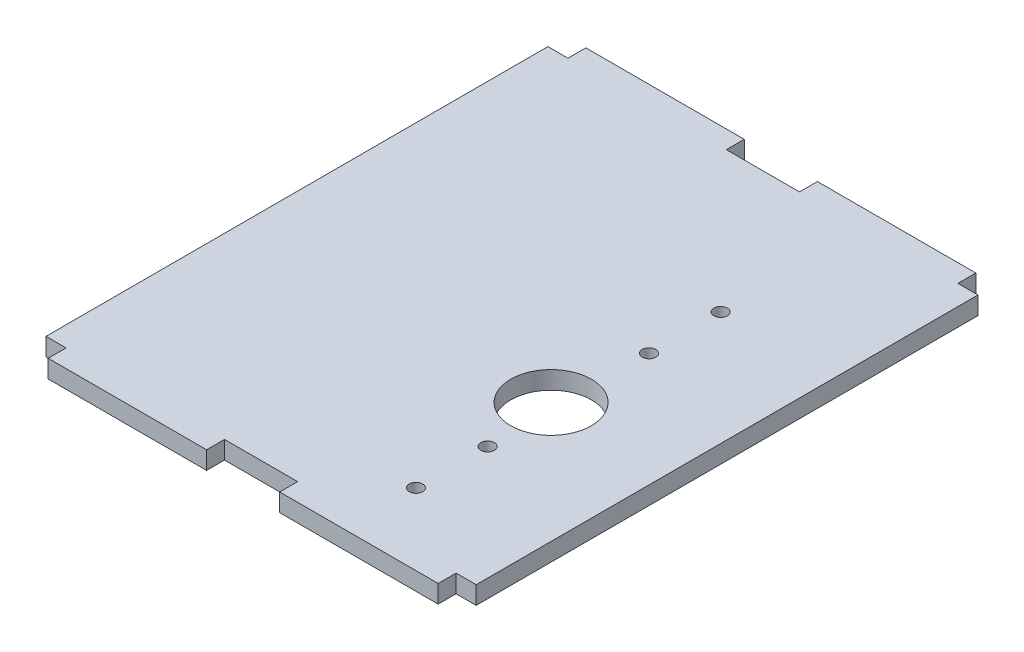
SolidWorks part; units mm, degrees
ref_plane "Front Plane" through (0, 0, 0) normal (0, 0, 1) x (1, 0, 0)
ref_plane "Top Plane" through (0, 0, 0) normal (0, 1, 0) x (1, 0, 0)
ref_plane "Right Plane" through (0, 0, 0) normal (1, 0, 0) x (0, 0, -1)
sketch "Sketch1" plane through (0, 0, 0) normal (0, 1, 0) x (1, 0, 0)
  line L1 (0, 0) -> (304.8, 0)
  line L2 (0, 0) -> (0, 355.6)
  line L3 (0, 355.6) -> (304.8, 355.6)
  line L4 (304.8, 0) -> (304.8, 355.6)
  ellipse E1 centre (219.5122, 138.3861) end of major axis (248.0872, 138.3861) minor radius 28.574
  dimension "D1" = 355.6
  dimension "D2" = 304.8
extrude "Boss-Extrude1" add sketch "Sketch1" along normal blind 12.7
sketch "Sketch2" plane through (0, 0, 0) normal (0, -1, 0) x (1, 0, 0)
  line L0 (0, 0) -> (304.8, 0) construction
  line L1 (0, -355.6) -> (0, 0) construction
  circle A0 centre (224.028, -38.1) radius 4.7625
  circle A1 centre (224.028, -88.9) radius 4.7625
  circle A2 centre (224.028, -203.2) radius 4.7625
  circle A3 centre (224.028, -254) radius 4.7625
  dimension "D3" = 88.9
  dimension "D6" = 9.525
  dimension "D1" = 38.1
  dimension "D2" = 224.028
  dimension "D4" = 203.2
  dimension "D5" = 254
  dimension "D7" = 224.028
  dimension "D8" = 224.028
  dimension "D9" = 224.028
extrude "Cut-Extrude1" cut sketch "Sketch2" against normal blind 12.7
sketch "Sketch3" plane through (0, 12.7, 0) normal (0, 1, 0) x (1, 0, 0)
  line L0 (152.4, 355.6) -> (152.4, 250.206) construction
  line L1 (0, 177.8) -> (22.2548, 177.8) construction
  line L2 (14.224, 355.6) -> (126.492, 355.6)
  line L3 (14.224, 355.6) -> (14.224, 368.3)
  line L4 (0, 355.6) -> (0, 0)
  line L5 (0, 0) -> (304.8, 0)
  line L6 (304.8, 0) -> (304.8, 355.6)
  line L7 (304.8, 355.6) -> (0, 355.6)
  line L8 (0, 355.6) -> (0, 0) construction
  line L9 (0, 0) -> (304.8, 0) construction
  line L10 (304.8, 0) -> (304.8, 355.6) construction
  line L11 (304.8, 355.6) -> (0, 355.6) construction
  line L12 (14.224, 368.3) -> (126.492, 368.3)
  line L13 (126.492, 355.6) -> (126.492, 368.3)
  line L14 (290.576, 368.3) -> (178.308, 368.3)
  line L15 (178.308, 355.6) -> (178.308, 368.3)
  line L16 (290.576, 355.6) -> (178.308, 355.6)
  line L17 (290.576, 355.6) -> (290.576, 368.3)
  line L18 (290.576, 0) -> (290.576, -12.7)
  line L19 (290.576, 0) -> (178.308, 0)
  line L20 (178.308, 0) -> (178.308, -12.7)
  line L21 (290.576, -12.7) -> (178.308, -12.7)
  line L22 (14.224, -12.7) -> (126.492, -12.7)
  line L23 (126.492, 0) -> (126.492, -12.7)
  line L24 (14.224, 0) -> (126.492, 0)
  line L25 (14.224, 0) -> (14.224, -12.7)
  dimension "D2" = 25.908
  dimension "D3" = 112.268
  dimension "D4" = 12.7
  dimension "D1" = 0
extrude "Boss-Extrude2" add sketch "Sketch3" against normal blind 12.7
sketch "Sketch4" plane through (0, 0, 0) normal (0, -1, 0) x (1, 0, 0)
  line L20 (0, 0) -> (0, -355.6)
  line L21 (0, -355.6) -> (14.224, -355.6)
  line L22 (14.224, -355.6) -> (14.224, -368.3)
  line L23 (14.224, -368.3) -> (126.492, -368.3)
  line L24 (126.492, -368.3) -> (126.492, -355.6)
  line L25 (126.492, -355.6) -> (178.308, -355.6)
  line L26 (178.308, -355.6) -> (178.308, -368.3)
  line L27 (178.308, -368.3) -> (290.576, -368.3)
  line L28 (290.576, -368.3) -> (290.576, -355.6)
  line L29 (290.576, -355.6) -> (304.8, -355.6)
  line L30 (304.8, -355.6) -> (304.8, 0)
  line L31 (304.8, 0) -> (290.576, 0)
  line L32 (290.576, 0) -> (290.576, 12.7)
  line L33 (290.576, 12.7) -> (178.308, 12.7)
  line L34 (178.308, 12.7) -> (178.308, 0)
  line L35 (178.308, 0) -> (126.492, 0)
  line L36 (126.492, 0) -> (126.492, 12.7)
  line L37 (126.492, 12.7) -> (14.224, 12.7)
  line L38 (14.224, 12.7) -> (14.224, 0)
  line L39 (14.224, 0) -> (0, 0)
  line L40 (0, 0) -> (0, -355.6)
  line L41 (0, -355.6) -> (14.224, -355.6)
  line L42 (14.224, -355.6) -> (14.224, -368.3)
  line L43 (14.224, -368.3) -> (126.492, -368.3)
  line L44 (126.492, -368.3) -> (126.492, -355.6)
  line L45 (126.492, -355.6) -> (178.308, -355.6)
  line L46 (178.308, -355.6) -> (178.308, -368.3)
  line L47 (178.308, -368.3) -> (290.576, -368.3)
  line L48 (290.576, -368.3) -> (290.576, -355.6)
  line L49 (290.576, -355.6) -> (304.8, -355.6)
  line L50 (304.8, -355.6) -> (304.8, 0)
  line L51 (304.8, 0) -> (290.576, 0)
  line L52 (290.576, 0) -> (290.576, 12.7)
  line L53 (290.576, 12.7) -> (178.308, 12.7)
  line L54 (178.308, 12.7) -> (178.308, 0)
  line L55 (178.308, 0) -> (126.492, 0)
  line L56 (126.492, 0) -> (126.492, 12.7)
  line L57 (126.492, 12.7) -> (14.224, 12.7)
  line L58 (14.224, 12.7) -> (14.224, 0)
  line L59 (14.224, 0) -> (0, 0)
  circle A5 centre (224.028, -203.2) radius 4.7625 construction
  circle A6 centre (224.028, -88.9) radius 4.7625 construction
  dimension "D3" = 109.5375
  dimension "D1" = 0
